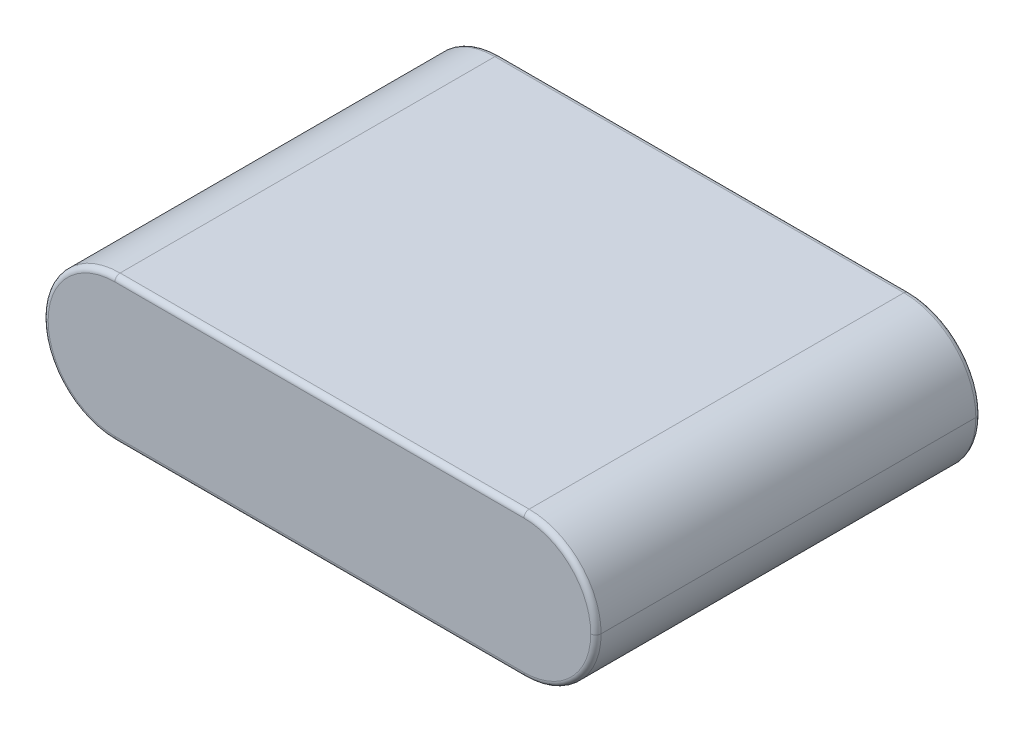
SolidWorks part; units mm, degrees
ref_plane "Plan de face" through (0, 0, 0) normal (0, 0, 1) x (1, 0, 0)
ref_plane "Plan de dessus" through (0, 0, 0) normal (0, 1, 0) x (1, 0, 0)
ref_plane "Plan de droite" through (0, 0, 0) normal (1, 0, 0) x (0, 0, -1)
sketch "Esquisse1" plane through (0, 0, 0) normal (0, 1, 0) x (1, 0, 0)
  line L1 (0, 0) -> (106.4, 0)
  line L2 (0, 0) -> (0, 74.1)
  line L3 (0, 74.1) -> (106.4, 74.1)
  line L4 (106.4, 0) -> (106.4, 74.1)
  dimension "D1" = 106.4
  dimension "D2" = 74.1
extrude "Boss.-Extru.1" add sketch "Esquisse1" along normal blind 27.7
fillet "Congé2" radius 13.85 4 edges at (0, 0, -37.05) (0, 27.7, -37.05) (106.4, 27.7, -37.05) (106.4, 0, -37.05)
fillet "Congé3" radius 1 12 edges at (53.2, 27.7, 0) (102.3434, 23.6434, 0) (102.3434, 4.0566, 0) (53.2, 0, 0) (4.0566, 4.0566, 0) (4.0566, 23.6434, 0) (102.3434, 4.0566, -74.1) (102.3434, 23.6434, -74.1) (53.2, 27.7, -74.1) (4.0566, 23.6434, -74.1) (4.0566, 4.0566, -74.1) (53.2, 0, -74.1)
